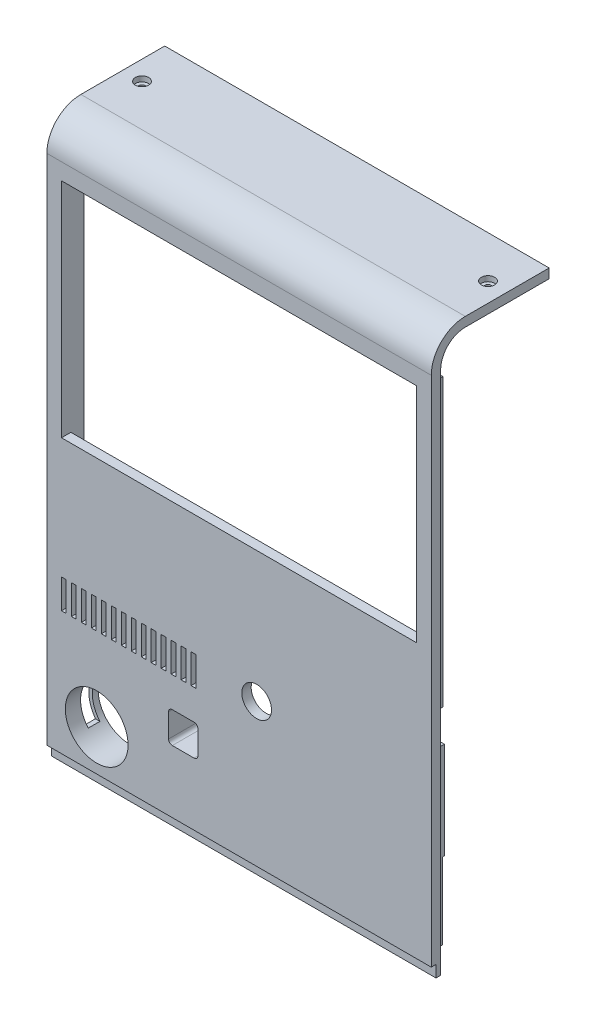
SolidWorks part; units mm, degrees
ref_plane "Alzado" through (0, 0, 0) normal (0, 0, 1) x (1, 0, 0)
ref_plane "Planta" through (0, 0, 0) normal (0, 1, 0) x (1, 0, 0)
ref_plane "Vista lateral" through (0, 0, 0) normal (1, 0, 0) x (0, 0, -1)
sketch "Croquis2" plane through (0, 0, 0) normal (1, 0, 0) x (0, 0, -1)
  line L0 (37, 0) -> (37, -3.2)
  line L1 (8.4, 0) -> (37, 0)
  line L2 (0, 8.4) -> (0, 239.6)
  line L3 (8.4, 248) -> (37, 248)
  line L5 (37, 248) -> (37, 251.2)
  line L6 (37, -3.2) -> (8.4, -3.2)
  line L7 (37, 251.2) -> (8.4, 251.2)
  line L8 (-3.2, 239.6) -> (-3.2, 8.4)
  arc A0 (8.4, 248) -> (0, 239.6) centre (8.4, 239.6) ccw
  arc A1 (0, 8.4) -> (8.4, 0) centre (8.4, 8.4) ccw
  arc A4 (8.4, 251.2) -> (-3.2, 239.6) centre (8.4, 239.6) ccw
  arc A5 (-3.2, 8.4) -> (8.4, -3.2) centre (8.4, 8.4) ccw
  point P9 (0, 0)
  dimension "D3" = 8.4
  dimension "D6" = 3.2
  dimension "D5" = 11.6
  dimension "D1" = 248
  dimension "D2" = 37
  dimension "D4" = 3.2
extrude "Saliente-Extruir1" add sketch "Croquis2" along normal blind 131.1
sketch "Croquis3" plane through (0, 251.2, 0) normal (0, 1, 0) x (1, 0, 0)
  line L0 (131.1, 37) -> (0, 37) construction
  line L1 (0, 37) -> (0, 8.4) construction
  line L2 (65.55, 37) -> (65.55, 8.4) construction
  line L4 (131.1, 8.4) -> (0, 8.4) construction
  circle A0 centre (6.55, 22.7) radius 1.1
  circle A1 centre (124.55, 22.7) radius 1.1
  dimension "D3" = 2.2
  dimension "D1" = 14.3
  dimension "D2" = 6.55
extrude "Cortar-Extruir1" cut sketch "Croquis3" against normal through all
sketch "Croquis4" plane through (0, 0, 3.2) normal (0, 0, 1) x (1, 0, 0)
  line L0 (131.1, 8.4) -> (0, 8.4) construction
  line L1 (0, 249.9) -> (0, 248) construction
  line L2 (65.55, 239.6) -> (65.55, 8.4) construction
  line L4 (5, 234) -> (126.1, 234)
  line L5 (126.1, 234) -> (126.1, 158.2)
  line L6 (126.1, 158.2) -> (5, 158.2)
  line L7 (5, 158.2) -> (5, 234)
  line L8 (0, 239.6) -> (0, 8.4) construction
  line L9 (131.1, 239.6) -> (0, 239.6) construction
  line L10 (8.4, 117) -> (8.4, 107)
  line L11 (41.5, 86.1) -> (51.5, 86.1)
  line L12 (41.5, 86.1) -> (41.5, 96.7)
  line L13 (41.5, 96.7) -> (51.5, 96.7)
  line L14 (51.5, 86.1) -> (51.5, 96.7)
  line L15 (5, 117) -> (6.6, 117)
  line L16 (5, 117) -> (5, 107)
  line L17 (5, 107) -> (6.6, 107)
  line L18 (6.6, 117) -> (6.6, 107)
  line L19 (8.4, 117) -> (10, 117)
  line L20 (10, 117) -> (10, 107)
  line L21 (8.4, 107) -> (10, 107)
  line L22 (11.8, 117) -> (11.8, 107)
  line L23 (11.8, 117) -> (13.4, 117)
  line L24 (13.4, 117) -> (13.4, 107)
  line L25 (11.8, 107) -> (13.4, 107)
  line L26 (15.2, 117) -> (15.2, 107)
  line L27 (15.2, 117) -> (16.8, 117)
  line L28 (16.8, 117) -> (16.8, 107)
  line L29 (15.2, 107) -> (16.8, 107)
  line L30 (18.6, 117) -> (18.6, 107)
  line L31 (18.6, 117) -> (20.2, 117)
  line L32 (20.2, 117) -> (20.2, 107)
  line L33 (18.6, 107) -> (20.2, 107)
  line L34 (22, 117) -> (22, 107)
  line L35 (22, 117) -> (23.6, 117)
  line L36 (23.6, 117) -> (23.6, 107)
  line L37 (22, 107) -> (23.6, 107)
  line L38 (25.4, 117) -> (25.4, 107)
  line L39 (25.4, 117) -> (27, 117)
  line L40 (27, 117) -> (27, 107)
  line L41 (25.4, 107) -> (27, 107)
  line L42 (28.8, 117) -> (28.8, 107)
  line L43 (28.8, 117) -> (30.4, 117)
  line L44 (30.4, 117) -> (30.4, 107)
  line L45 (28.8, 107) -> (30.4, 107)
  line L46 (32.2, 117) -> (32.2, 107)
  line L47 (32.2, 117) -> (33.8, 117)
  line L48 (33.8, 117) -> (33.8, 107)
  line L49 (32.2, 107) -> (33.8, 107)
  line L50 (35.6, 117) -> (35.6, 107)
  line L51 (35.6, 117) -> (37.2, 117)
  line L52 (37.2, 117) -> (37.2, 107)
  line L53 (35.6, 107) -> (37.2, 107)
  line L54 (39, 117) -> (39, 107)
  line L55 (39, 117) -> (40.6, 117)
  line L56 (40.6, 117) -> (40.6, 107)
  line L57 (39, 107) -> (40.6, 107)
  line L58 (42.4, 117) -> (42.4, 107)
  line L59 (42.4, 117) -> (44, 117)
  line L60 (44, 117) -> (44, 107)
  line L61 (42.4, 107) -> (44, 107)
  line L62 (45.8, 117) -> (45.8, 107)
  line L63 (45.8, 117) -> (47.4, 117)
  line L64 (47.4, 117) -> (47.4, 107)
  line L65 (45.8, 107) -> (47.4, 107)
  line L66 (49.2, 117) -> (49.2, 107)
  line L67 (49.2, 117) -> (50.8, 117)
  line L68 (50.8, 117) -> (50.8, 107)
  line L69 (49.2, 107) -> (50.8, 107)
  circle A0 centre (17, 78.7) radius 10.7
  circle A1 centre (71.55, 113.5) radius 5.07
  point P0 (5, 234)
  point P9 (126.1, 234)
  dimension "D6" = 21.4
  dimension "D16" = 10.14
  dimension "D2" = 121.1
  dimension "D3" = 75.8
  dimension "D4" = 17
  dimension "D5" = 169.3
  dimension "D7" = 24.5
  dimension "D8" = 151.3
  dimension "D9" = 10
  dimension "D10" = 10.6
  dimension "D11" = 131
  dimension "D12" = 10
  dimension "D13" = 1.6
  dimension "D14" = 5
  dimension "D17" = 134.5
  dimension "D18" = 14
  dimension "D19" = 6
  dimension "D15" = 14
extrude "Cortar-Extruir2" cut sketch "Croquis4" against normal through all
sketch "Croquis7" plane through (0, 0, 0) normal (0, 0, -1) x (-1, 0, 0)
  line L5 (-127.46, 125.3) -> (-127.96, 125.3)
  line L10 (-126.1, 234) -> (-127.46, 234)
  line L11 (-126.1, 234) -> (-126.1, 136)
  line L12 (-126.1, 136) -> (-127.46, 136)
  line L13 (-127.46, 234) -> (-127.46, 136)
  line L14 (-5, 234) -> (-3.64, 234)
  line L15 (-5, 234) -> (-5, 136)
  line L16 (-5, 136) -> (-3.64, 136)
  line L17 (-3.64, 234) -> (-3.64, 136)
  line L18 (-127.46, 125.3) -> (-126.1, 125.3)
  line L20 (-127.46, 66.3) -> (-126.1, 66.3)
  line L21 (-126.1, 125.3) -> (-126.1, 66.3)
  line L22 (-3.64, 125.3) -> (-5, 125.3)
  line L24 (-3.64, 66.3) -> (-5, 66.3)
  line L25 (-5, 125.3) -> (-5, 66.3)
  line L27 (-127.46, 66.3) -> (-127.96, 66.3)
  line L28 (-127.96, 125.3) -> (-127.96, 66.3)
  line L29 (-3.64, 125.3) -> (-3.14, 125.3)
  line L31 (-3.64, 66.3) -> (-3.14, 66.3)
  line L32 (-3.14, 125.3) -> (-3.14, 66.3)
  line L33 (-126.1, 53.5) -> (-127.96, 53.5)
  line L34 (-126.1, 53.5) -> (-126.1, 11.9)
  line L35 (-126.1, 11.9) -> (-127.96, 11.9)
  line L36 (-127.96, 53.5) -> (-127.96, 11.9)
  line L37 (-5, 53.5) -> (-3.14, 53.5)
  line L38 (-5, 53.5) -> (-5, 11.9)
  line L39 (-5, 11.9) -> (-3.14, 11.9)
  line L40 (-3.14, 53.5) -> (-3.14, 11.9)
  dimension "D1" = 1.36
  dimension "D2" = 98
  dimension "D3" = 10.7
  dimension "D4" = 59
  dimension "D5" = 0.5
  dimension "D6" = 0.5
  dimension "D7" = 12.8
  dimension "D8" = 1.36
  dimension "D9" = 1.36
  dimension "D10" = 0.5
  dimension "D11" = 1.36
  dimension "D12" = 41.6
extrude "Saliente-Extruir2" add sketch "Croquis7" along normal blind 4.4
sketch "Croquis8" plane through (0, 251.2, 0) normal (0, 1, 0) x (1, 0, 0)
  circle A0 centre (6.55, 22.7) radius 2.27
  circle A1 centre (124.55, 22.7) radius 2.27
  dimension "D1" = 4.54
extrude "Cortar-Extruir3" cut sketch "Croquis8" against normal blind 1.8
sketch "Croquis9" plane through (0, -3.2, 0) normal (0, -1, 0) x (1, 0, 0)
  circle A0 centre (124.55, -22.7) radius 2.27
  circle A1 centre (6.55, -22.7) radius 2.27
  dimension "D1" = 4.54
extrude "Cortar-Extruir4" cut sketch "Croquis9" against normal blind 1.8
sketch "Croquis10" plane through (0, 0, 0) normal (0, 0, -1) x (-1, 0, 0)
  line L0 (-41.5, 86.1) -> (-51.5, 86.1) construction
  line L1 (-51.5, 96.7) -> (-41.5, 96.7)
  line L2 (-51.5, 96.7) -> (-51.5, 86.1)
  line L3 (-51.5, 86.1) -> (-41.5, 86.1)
  line L4 (-41.5, 96.7) -> (-41.5, 86.1)
  line L5 (-52.7, 97.9) -> (-40.3, 97.9)
  line L6 (-40.3, 97.9) -> (-40.3, 84.9)
  line L7 (-40.3, 84.9) -> (-52.7, 84.9)
  line L8 (-52.7, 84.9) -> (-52.7, 97.9)
  line L9 (-41.5, 96.7) -> (-41.5, 86.1) construction
  circle A0 centre (-17, 78.7) radius 11.9
  circle A1 centre (-17, 78.7) radius 10.7 construction
  circle A2 centre (-17, 78.7) radius 10.7
  dimension "D1" = 1.2
  dimension "D2" = 1.2
  dimension "D3" = 1.2
  dimension "D4" = 1.2
  dimension "D5" = 1.2
extrude "Saliente-Extruir4" add sketch "Croquis10" along normal blind 8
fillet "Redondeo2" radius 1.28 4 edges at (51.5, 86.1, -2.4) (51.5, 96.7, -2.4) (41.5, 96.7, -2.4) (41.5, 86.1, -2.4)
ref_plane "Plano1" through (-10, 0, 0) normal (-1, 0, 0) x (0, 0, 1)
sketch "Croquis11" plane through (-10, 0, 0) normal (-1, 0, 0) x (0, 0, 1)
  line L0 (-8, 78.7) -> (0, 78.7) construction
  line L1 (-8, 90.6) -> (-8, 66.8) construction
  line L4 (-6, 71.7) -> (-2, 71.7)
  line L5 (-6, 71.7) -> (-6, 85.7)
  line L6 (-6, 85.7) -> (-2, 85.7)
  line L7 (-2, 71.7) -> (-2, 85.7)
  line L8 (-6, 71.7) -> (-2, 85.7) construction
  line L9 (-6, 85.7) -> (-2, 71.7) construction
  line L10 (0, 8.4) -> (0, 239.6) construction
  point P6 (-4, 78.7)
  dimension "D1" = 4
  dimension "D2" = 14
extrude "Cortar-Extruir5" cut sketch "Croquis11" against normal up to surface (18.9074 mm away) up to face at (27.7, 78.7, 3.2)
sketch "Croquis13" plane through (0, 0, -8) normal (0, 0, -1) x (-1, 0, 0)
  line L0 (-50.22, 96.7) -> (-42.78, 96.7)
  line L1 (-50.22, 86.1) -> (-42.78, 86.1)
  line L2 (-41.5, 87.38) -> (-41.5, 95.42)
  line L3 (-51.5, 87.38) -> (-51.5, 95.42)
  line L4 (-52.7, 97.9) -> (-52.7, 84.9)
  line L5 (-52.7, 84.9) -> (-40.3, 84.9)
  line L6 (-40.3, 84.9) -> (-40.3, 97.9)
  line L7 (-40.3, 97.9) -> (-52.7, 97.9)
  line L8 (-52.7, 97.9) -> (-52.7, 84.9)
  line L9 (-52.7, 84.9) -> (-40.3, 84.9)
  line L10 (-40.3, 84.9) -> (-40.3, 97.9)
  line L11 (-40.3, 97.9) -> (-52.7, 97.9)
  circle A0 centre (-50.22, 95.42) radius 1.28
  circle A1 centre (-50.22, 87.38) radius 1.28
  circle A2 centre (-42.78, 87.38) radius 1.28
  circle A3 centre (-42.78, 95.42) radius 1.28
  line M5 (-52.7, 97.9) -> (-52.7, 84.9)
  line M6 (-52.7, 84.9) -> (-40.3, 84.9)
  line M7 (-40.3, 84.9) -> (-40.3, 97.9)
  line M8 (-40.3, 97.9) -> (-52.7, 97.9)
  line M9 (-51.5, 87.38) -> (-51.5, 95.42)
  arc M10 (-51.5, 95.42) -> (-50.22, 96.7) centre (-50.22, 95.42) cw
  line M11 (-50.22, 96.7) -> (-42.78, 96.7)
  arc M12 (-42.78, 96.7) -> (-41.5, 95.42) centre (-42.78, 95.42) cw
  line M13 (-41.5, 95.42) -> (-41.5, 87.38)
  arc M14 (-41.5, 87.38) -> (-42.78, 86.1) centre (-42.78, 87.38) cw
  line M15 (-42.78, 86.1) -> (-50.22, 86.1)
  arc M16 (-50.22, 86.1) -> (-51.5, 87.38) centre (-50.22, 87.38) cw
  dimension "D1" = 0
extrude "Saliente-Extruir6" add sketch "Croquis13" along normal blind 0.2 contours M8 M5 M6 M7 M16 M9 M10 M11 M12 M13 M14 M15 region at (46.5, 97.7203, -8)
sketch "Croquis14" plane through (0, 0, 0) normal (0, 0, -1) x (-1, 0, 0)
  line L0 (-71.55, 113.5) -> (-71.55, 74.9205) construction
  circle A0 centre (-71.55, 88.8) radius 1.5
  circle A1 centre (-71.55, 88.8) radius 3.2
  dimension "D2" = 3
  dimension "D3" = 6.4
  dimension "D1" = 24.7
extrude "Saliente-Extruir7" add sketch "Croquis14" along normal blind 8.4
fillet "Redondeo3" radius 3.84 1 edges at (74.75, 88.8, 0)
sketch "Croquis17" plane through (127.46, 0, 0) normal (1, 0, 0) x (0, 0, -1)
  line L0 (4.4, 234) -> (4.4, 136) construction
  line L1 (0, 234) -> (4.4, 234)
  line L2 (0, 234) -> (0, 233.6)
  line L3 (0, 233.6) -> (4.4, 233.6)
  line L4 (4.4, 234) -> (4.4, 233.6)
  dimension "D1" = 0.4
extrude "Cortar-Extruir6" cut sketch "Croquis17" against normal through all
fillet "Redondeo4" radius 1.6 2 edges at (52.7, 91.4, 0) (40.3, 91.4, 0)
sketch "Croquis19" plane through (0, 0, 0) normal (0, 0, -1) x (-1, 0, 0)
  line L5 (-17, 66.8) -> (-17, 78.7) construction
  line L18 (-17, 78.7) -> (-17, 90.6) construction
  circle A2 centre (-17, 78.7) radius 11.9 construction
  circle A3 centre (-17, 90.6) radius 1.12
  circle A4 centre (-17, 66.8) radius 1.12
  dimension "D1" = 2.24
extrude "Saliente-Extruir8" add sketch "Croquis19" along normal up to surface (8 mm away) up to face at (5.1, 78.7, -8)
fillet "Redondeo5" radius 1 1 edges at (28.9, 78.7, 0)
sketch "Croquis21" plane through (127.96, 0, 0) normal (1, 0, 0) x (0, 0, -1)
  line L1 (4.4, 66.3) -> (3.8, 66.3)
  line L2 (4.4, 66.3) -> (4.4, 92.3)
  line L3 (4.4, 92.3) -> (3.8, 92.3)
  line L4 (3.8, 66.3) -> (3.8, 92.3)
  dimension "D1" = 0.6
  dimension "D2" = 26
extrude "Cortar-Extruir8" cut sketch "Croquis21" against normal up to vertex up to point (126.1, 66.3, -4.4)
sketch "Croquis23" plane through (0, 0, 3.2) normal (0, 0, 1) x (1, 0, 0)
  line L0 (126.1, 158.2) -> (126.1, 234) construction
  line L1 (5, 158.2) -> (126.1, 158.2)
  line L2 (5, 158.2) -> (5, 158.1)
  line L3 (5, 158.1) -> (126.1, 158.1)
  line L4 (126.1, 158.2) -> (126.1, 158.1)
  dimension "D1" = 0.1
extrude "Cortar-Extruir9" cut sketch "Croquis23" against normal through all
sketch "Croquis24" plane through (131.1, 0, 0) normal (1, 0, 0) x (0, 0, -1)
  line L0 (-16.4896, 64.8) -> (22.0591, 64.8) construction
  line L1 (8.4, -3.2) -> (37, -3.2) construction
  line L2 (-3.2, 64.8) -> (-1.6, 64.8)
  line L3 (-3.2, 239.6) -> (-3.2, 8.4) construction
  line L4 (-1.6, 64.8) -> (-1.6, 60.8)
  line L5 (-1.6, 60.8) -> (37, 60.8)
  line L6 (37, 60.8) -> (37, -3.2)
  line L7 (37, -3.2) -> (-3.5072, -3.2)
  line L8 (-3.5072, -3.2) -> (-3.5072, 64.8)
  line L9 (-3.5072, 64.8) -> (-3.2, 64.8)
  line L10 (37, -3.2) -> (37, 0) construction
  dimension "D1" = 68
  dimension "D2" = 4
  dimension "D3" = 1.6
extrude "Cortar-Extruir10" cut sketch "Croquis24" against normal through all
sketch "Croquis25" [suppressed] plane through (131.1, 0, 0) normal (1, 0, 0) x (0, 0, -1)
  line L0 (-3.2, 64.8) -> (-1.6, 64.8)
  line L1 (-3.2, 239.6) -> (-3.2, 8.4) construction
  line L2 (-1.6, 64.8) -> (-1.6, 60.8)
  line L3 (-1.6, 60.8) -> (37, 60.8)
  line L4 (37, 60.8) -> (37, -3.2)
  line L5 (37, -3.2) -> (-3.3411, -3.2)
  line L6 (-3.3411, -3.2) -> (-3.3411, 64.8)
  line L7 (-3.3411, 64.8) -> (-3.2, 64.8)
  line L8 (8.4, -3.2) -> (37, -3.2) construction
  line L9 (37, -3.2) -> (37, 0) construction
  line L10 (37, 60.8) -> (37, 266.4059)
  line L11 (37, 266.4059) -> (-3.3411, 266.4059)
  line L12 (-3.3411, 266.4059) -> (-3.3411, 64.8)
  line M8 (37, 248) -> (37, 251.2)
  line M9 (37, 251.2) -> (8.4, 251.2)
  arc M10 (8.4, 251.2) -> (-3.2, 239.6) centre (8.4, 239.6) ccw
  line M11 (-3.2, 239.6) -> (-3.2, 8.4)
  line M17 (0, 8.4) -> (0, 239.6)
  arc M18 (0, 239.6) -> (8.4, 248) centre (8.4, 239.6) cw
  line M19 (8.4, 248) -> (37, 248)
  dimension "D1" = 68
  dimension "D2" = 4
  dimension "D3" = 1.6
extrude "Cortar-Extruir11" [suppressed] cut sketch "Croquis25" against normal through all contours L3 L10 M19 M18 M17 | L2 L3 L0 M17 M18 M19 M8 M9 M10 M11
